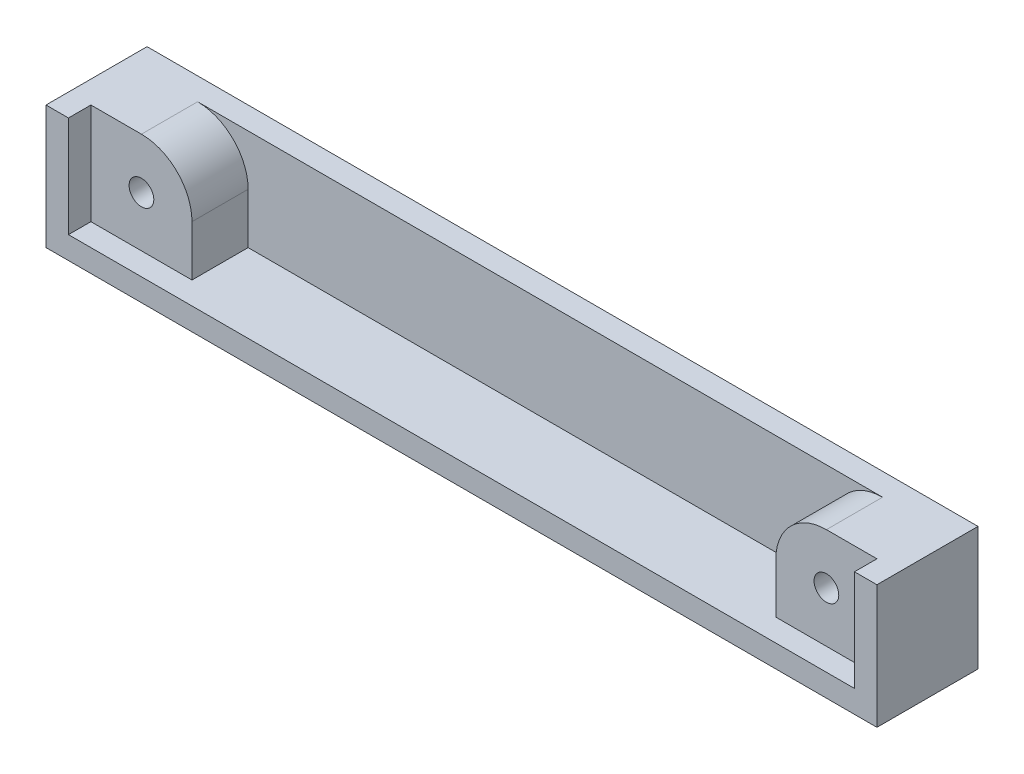
SolidWorks part; units mm, degrees
ref_plane "Спереди" through (0, 0, 0) normal (0, 0, 1) x (1, 0, 0)
ref_plane "Сверху" through (0, 0, 0) normal (0, 1, 0) x (1, 0, 0)
ref_plane "Справа" through (0, 0, 0) normal (1, 0, 0) x (0, 0, -1)
other "Configuration Table"
sketch "Эскиз1" plane through (0, 0, 0) normal (0, 0, 1) x (1, 0, 0)
  line L0 (2, 6.5) -> (72, 6.5) construction
  line L1 (0, 0) -> (74, 0)
  line L2 (0, 0) -> (0, 11)
  line L3 (0, 11) -> (74, 11)
  line L4 (74, 0) -> (74, 11)
  line L5 (2, 11) -> (72, 11)
  line L6 (2, 11) -> (2, 2)
  line L7 (2, 2) -> (72, 2)
  line L8 (72, 11) -> (72, 2)
  line L9 (6.5, 11) -> (6.5, 2) construction
  line L10 (67.5, 11) -> (67.5, 2) construction
  line L11 (63, 11) -> (63, 2)
  line L12 (11, 11) -> (11, 2)
  circle A0 centre (6.5, 6.5) radius 1.1
  circle A1 centre (67.5, 6.5) radius 1.1
  dimension "D10" = 2.2
  dimension "D11" = 2.2
  dimension "D1" = 70
  dimension "D2" = 2
  dimension "D3" = 2
  dimension "D4" = 2
  dimension "D5" = 9
  dimension "D6" = 4.5
  dimension "D7" = 4.5
  dimension "D8" = 9
  dimension "D9" = 9
extrude "Бобышка-Вытянуть1" add sketch "Эскиз1" along normal blind 7 contours L12 L3 L6 L7 A0 | L5 L11 L7 L8 A1 region at (6.5, 10.8727, 0) region at (71.8727, 6.5, 0)
extrude "Бобышка-Вытянуть2" add sketch "Эскиз1<3>" along normal blind 2 contours L5 L12 L7 L11 region at (37, 6.5, 0)
sketch "Эскиз1<3>" plane through (0, 0, 0) normal (0, 0, 1) x (1, 0, 0) same geometry as "Эскиз1"
extrude "Бобышка-Вытянуть3" add sketch "Эскиз1<4>" along normal blind 9 contours L3 L8 L7 L6 L2 L1 L4 region at (0.7481, 5.5, 0)
sketch "Эскиз1<4>" plane through (0, 0, 0) normal (0, 0, 1) x (1, 0, 0) same geometry as "Эскиз1"
fillet "Скругление1" radius 4.5 2 edges at (63, 11, 4.5) (11, 11, 4.5)
